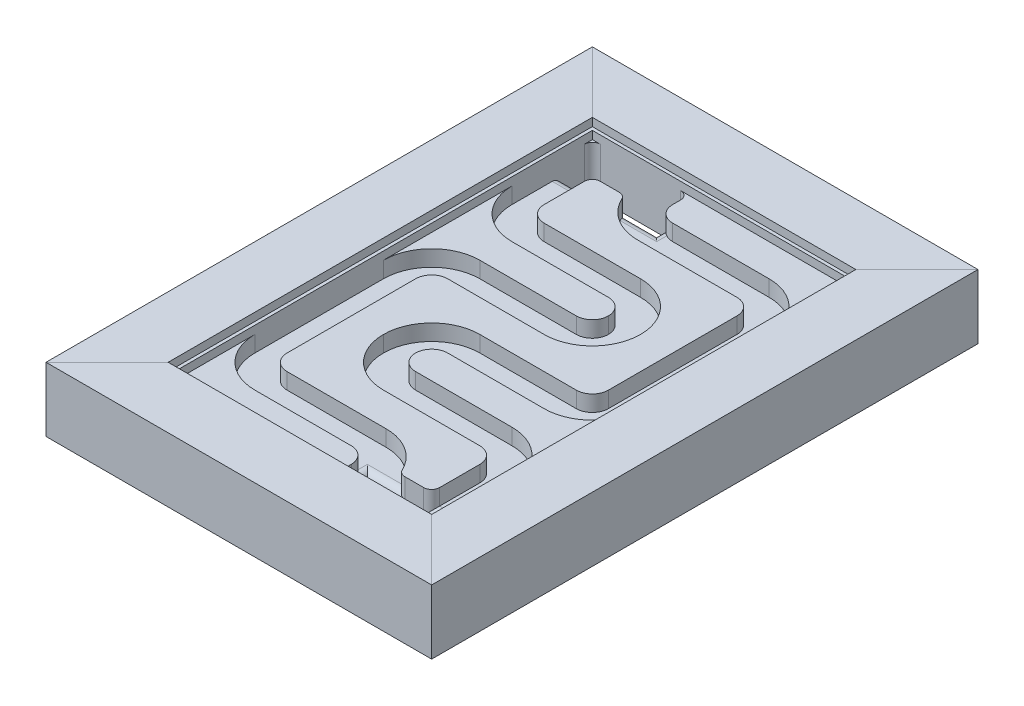
SolidWorks part; units mm, degrees
ref_plane "Ebene vorne" through (0, 0, 0) normal (0, 0, 1) x (1, 0, 0)
ref_plane "Ebene oben" through (0, 0, 0) normal (0, 1, 0) x (1, 0, 0)
ref_plane "Ebene rechts" through (0, 0, 0) normal (1, 0, 0) x (0, 0, -1)
sketch "Skizze1" plane through (0, 0, 0) normal (0, 1, 0) x (1, 0, 0)
  line L1 (0, 0) -> (12, 0)
  line L2 (0, 0) -> (0, 17)
  line L3 (0, 17) -> (12, 17)
  line L4 (12, 0) -> (12, 17)
  dimension "D1" = 17
  dimension "D2" = 12
extrude "Aufsatz-Linear austragen1" add sketch "Skizze1" along normal blind 2
sketch "Skizze2" plane through (0, 2, 0) normal (0, 1, 0) x (1, 0, 0)
  line L0 (0, 17) -> (0, 0) construction
  line L1 (10, 15) -> (2, 15)
  line L2 (10, 15) -> (10, 2)
  line L3 (10, 2) -> (2, 2)
  line L4 (2, 15) -> (2, 2)
  line L5 (0, 0) -> (12, 0) construction
  dimension "D1" = 13
  dimension "D2" = 8
  dimension "D3" = 2
  dimension "D4" = 2
sketch "Skizze4" plane through (0, 2, 0) normal (0, 1, 0) x (1, 0, 0)
  line L1 (10, 3) -> (7, 3)
  line L2 (10, 3) -> (10, 2)
  line L3 (10, 2) -> (7, 2)
  line L4 (7, 3) -> (7, 2)
  line L5 (2, 14) -> (5, 14)
  line L6 (2, 14) -> (2, 15)
  line L7 (2, 15) -> (5, 15)
  line L8 (5, 14) -> (5, 15)
  dimension "D1" = 1
  dimension "D2" = 3
  dimension "D3" = 3
  dimension "D4" = 1
sketch "Skizze3" plane through (0, 2, 0) normal (0, 1, 0) x (1, 0, 0)
  line L0 (2, 14) -> (2, 11)
  line L1 (2, 14) -> (3, 14)
  line L3 (3, 14) -> (3, 12)
  line L4 (3, 12) -> (8, 12)
  line L5 (4, 14) -> (4, 13)
  line L6 (4, 13) -> (9, 13)
  line L7 (8, 12) -> (8, 9)
  line L8 (8, 9) -> (3, 9)
  line L9 (2, 11) -> (7, 11)
  line L10 (7, 11) -> (7, 10)
  line L11 (7, 10) -> (2, 10)
  line L14 (4, 14) -> (10, 14)
  line L15 (10, 14) -> (10, 7)
  line L16 (9, 13) -> (9, 8)
  line L17 (9, 8) -> (4, 8)
  line L18 (4, 8) -> (4, 5)
  line L19 (10, 7) -> (5, 7)
  line L25 (5, 7) -> (5, 6)
  line L26 (5, 6) -> (10, 6)
  line L27 (10, 6) -> (10, 3)
  line L28 (10, 3) -> (9, 3)
  line L29 (9, 3) -> (9, 5)
  line L30 (9, 5) -> (4, 5)
  line L31 (2, 10) -> (2, 3)
  line L32 (2, 3) -> (8, 3)
  line L33 (8, 3) -> (8, 4)
  line L34 (8, 4) -> (3, 4)
  line L35 (3, 4) -> (3, 9)
  dimension "D1" = 1
  dimension "D2" = 1
  dimension "D3" = 1
  dimension "D4" = 1
  dimension "D5" = 3
  dimension "D6" = 7
  dimension "D7" = 1
  dimension "D8" = 7
  dimension "D9" = 3
  dimension "D10" = 1
  dimension "D11" = 1
  dimension "D12" = 6
  dimension "D13" = 1
  dimension "D14" = 1
  dimension "D15" = 1
  dimension "D16" = 1
  dimension "D17" = 6
  dimension "D18" = 6
  dimension "D19" = 6
  dimension "D20" = 1
  dimension "D21" = 1
  dimension "D22" = 1
  dimension "D23" = 6
  dimension "D24" = 6
  dimension "D25" = 1
  dimension "D26" = 8
extrude "Schnitt-Linear austragen1" cut sketch "Skizze4" against normal through all and the other way through all contours L1 L4 L3 L2 | L8 L7 L6 L5 region at (8.5, 2, -2.5)
extrude "Schnitt-Linear austragen3" cut sketch "Skizze3" against normal blind 1 contours L34 L35 L8 L7 L4 L3 L1 L0 L9 L10 L11 L31 L32 L33 | L30 L29 L28 L27 L26 L25 L19 L15 L14 L5 L6 L16 L17 L18 region at (2.5, 2, -13.8747) region at (7, 2, -13.8747)
fillet "Verrundung1" radius 0.5 12 edges at (3, 1.5, -12) (3, 1.5, -9) (3, 1.5, -4) (5, 1.5, -6) (5, 1.5, -7) (9, 1.5, -13) (7, 1.5, -10) (7, 1.5, -11) (9, 1.5, -8) (9, 1.5, -5) (5, 1.5, -14) (7, 1.5, -3)
fillet "Verrundung2" radius 1.5 12 edges at (4, 1.5, -8) (8, 1.5, -4) (4, 1.5, -13) (10, 1.5, -14) (2, 1.5, -11) (10, 1.5, -7) (10, 1.5, -6) (2, 1.5, -3) (2, 1.5, -10) (8, 1.5, -12) (8, 1.5, -9) (4, 1.5, -5)
fillet "Verrundung3" radius 0.25 14 edges at (9.5, 1, -3) (7.5, 1, -3) (7, 1, -2.75) (5, 1, -14.25) (4.5, 1, -14) (2.5, 1, -14) (4, 1.5, -14) (3, 1.5, -14) (2, 1, -15) (5, 1, -15) (9, 1.5, -3) (8, 1.5, -3) (10, 1, -2) (7, 1, -2)
extrude "Schnitt-Linear austragen4" cut sketch "Skizze2" against normal blind 0.5 contours L1 L4 L3 L2
sketch "Skizze6" plane through (0, 2, 0) normal (0, 1, 0) x (1, 0, 0)
  line L1 (1.9, 15.1) -> (10.1, 15.1)
  line L2 (1.9, 15.1) -> (1.9, 1.9)
  line L3 (1.9, 1.9) -> (10.1, 1.9)
  line L4 (10.1, 15.1) -> (10.1, 1.9)
  line L5 (2, 15) -> (10, 15)
  line L6 (2, 15) -> (2, 2)
  line L7 (2, 2) -> (10, 2)
  line L8 (10, 15) -> (10, 2)
  dimension "D1" = 0.1
  dimension "D2" = 0.1
  dimension "D3" = 0.1
  dimension "D4" = 0.1
extrude "Schnitt-Linear austragen5" cut sketch "Skizze6" against normal blind 0.25
sketch "Skizze7" plane through (0, 2, 0) normal (0, 1, 0) x (1, 0, 0)
  line L0 (1.9, 15.1) -> (0, 17)
  line L1 (0, 17) -> (0, 0)
  line L2 (0, 0) -> (1.9, 1.9)
  line L3 (1.9, 1.9) -> (1.9, 15.1)
  line L4 (10.1, 15.1) -> (12, 17)
  line L5 (12, 17) -> (12, 0)
  line L6 (12, 0) -> (10.1, 1.9)
  line L7 (10.1, 1.9) -> (10.1, 15.1)
extrude "Schnitt-Linear austragen6" cut sketch "Skizze7" against normal through all
sketch "Skizze8" plane through (0, 2, 0) normal (0, 1, 0) x (1, 0, 0)
  line L0 (0, 17) -> (0, 0)
  line L1 (0, 0) -> (1.9, 1.9)
  line L2 (1.9, 1.9) -> (1.9, 15.1)
  line L3 (1.9, 15.1) -> (0, 17)
  line L4 (10.1, 15.1) -> (10.1, 1.9)
  line L5 (10.1, 1.9) -> (12, 0)
  line L6 (12, 0) -> (12, 17)
  line L7 (12, 17) -> (10.1, 15.1)
extrude "Aufsatz-Linear austragen2" add sketch "Skizze8" against normal blind 2 separate body
